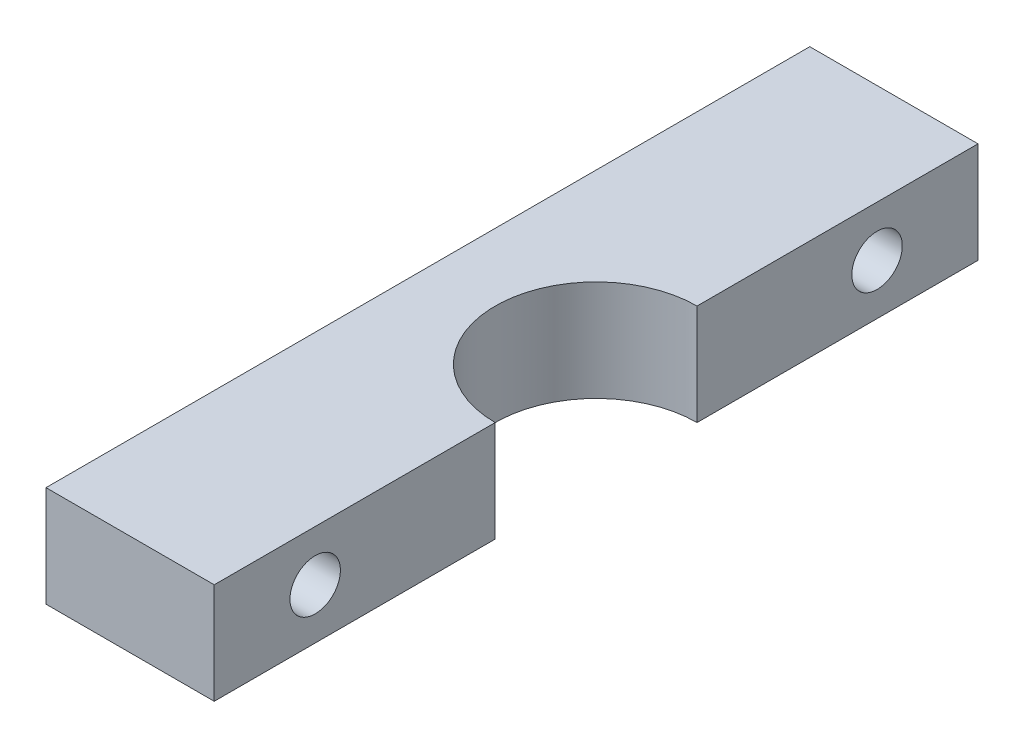
SolidWorks part; units mm, degrees
ref_plane "Płaszczyzna przednia" through (0, 0, 0) normal (0, 0, 1) x (1, 0, 0)
ref_plane "Płaszczyzna górna" through (0, 0, 0) normal (0, 1, 0) x (1, 0, 0)
ref_plane "Płaszczyzna prawa" through (0, 0, 0) normal (1, 0, 0) x (0, 0, -1)
sketch "Sketch1" plane through (0, 0, 0) normal (0, 1, 0) x (1, 0, 0)
  line L0 (10, 28.7) -> (10, 45.4)
  line L1 (0, 0) -> (10, 0)
  line L2 (0, 0) -> (0, 45.4)
  line L3 (0, 45.4) -> (10, 45.4)
  line L4 (10, 0) -> (10, 16.7)
  line L5 (0, 0) -> (10, 45.4) construction
  line L6 (0, 45.4) -> (10, 0) construction
  line L7 (-4.8209, 22.7) -> (14.8209, 22.7) construction
  line L8 (10, 0) -> (10, 45.4) construction
  arc A0 (10, 28.7) -> (10, 16.7) centre (10, 22.7) ccw
  point P4 (5, 22.7)
  point P12 (5, 22.7)
  dimension "D3" = 12
  dimension "D1" = 45.4
  dimension "D2" = 10
extrude "Boss-Extrude1" add sketch "Sketch1" along normal blind 6
hole_wizard "Ø3.0 (3) Diameter Hole1" positions "Sketch2" profile "Sketch3" hole size "Ø3.0" standard "ANSI Metric" end condition through all
sketch "Sketch2" plane through (0, 0, 0) normal (-1, 0, 0) x (0, 0, 1)
  line L0 (0, 6) -> (0, 0) construction
  line L2 (-45.4, 6) -> (0, 6) construction
  line L3 (-45.4, 6) -> (-45.4, 0) construction
  point P0 (-6, 3)
  point P2 (-39.4, 3)
  dimension "D1" = 6
  dimension "D2" = 3
  dimension "D3" = 6
sketch "Sketch3" plane through (0, 3, -6) normal (0, 1, 0) x (0, 0, 1)
  line L0 (0, 0) -> (0, 10)
  line L1 (0, 10) -> (1.5, 10)
  line L2 (1.5, 10) -> (1.5, 0)
  line L5 (1.5, 0) -> (0, 0)
  line L11 (0, -6.35) -> (0, 107.95) construction
  dimension "Thru Hole Dia." = 3
  dimension "Thru Hole Depth" = 10
